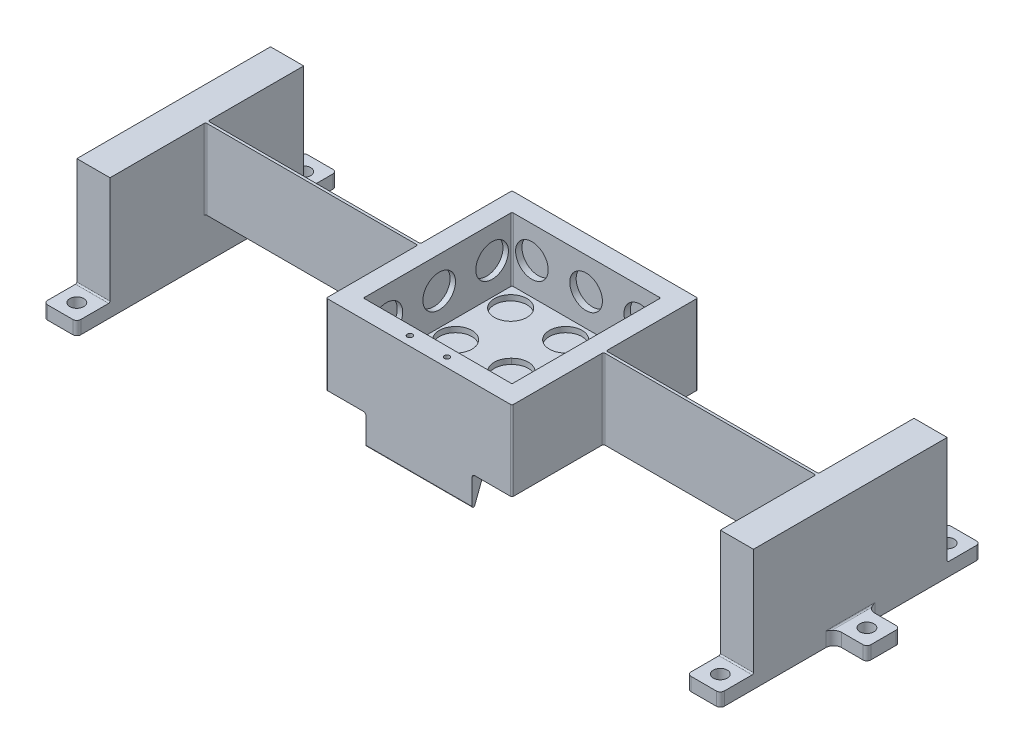
SolidWorks part; units mm, degrees
ref_plane "Front Plane" through (0, 0, 0) normal (0, 0, 1) x (1, 0, 0)
ref_plane "Top Plane" through (0, 0, 0) normal (0, 1, 0) x (1, 0, 0)
ref_plane "Right Plane" through (0, 0, 0) normal (1, 0, 0) x (0, 0, -1)
sketch "Sketch1" plane through (0, 0, 0) normal (0, 1, 0) x (1, 0, 0)
  line L1 (-35, -35) -> (35, -35)
  line L2 (-35, -35) -> (-35, 35)
  line L3 (-35, 35) -> (35, 35)
  line L4 (35, -35) -> (35, 35)
  line L5 (-35, -35) -> (35, 35) construction
  line L6 (-35, 35) -> (35, -35) construction
  point P0 (0, 0)
  dimension "D1" = 70
  dimension "D2" = 70
extrude "Boss-Extrude1" add sketch "Sketch1" along normal blind 30
shell "Shell1" thickness 7 removed face at (0, 30, 0)
sketch "Sketch2" plane through (0, 30, 0) normal (0, 1, 0) x (1, 0, 0)
  line L0 (-35, 35) -> (-35, -35) construction
  line L1 (-28, -28) -> (28, -28) construction
  line L2 (-28, -28) -> (-28, 28) construction
  line L3 (-28, 28) -> (28, 28) construction
  line L4 (28, -28) -> (28, 28) construction
  line L5 (-28, -28) -> (28, 28) construction
  line L6 (-28, 28) -> (28, -28) construction
  line L7 (35, 35) -> (-35, 35) construction
  point P0 (0, 0)
  dimension "D1" = 7
  dimension "D2" = 7
sketch "Sketch3" plane through (35, 0, 0) normal (1, 0, 0) x (0, 0, -1)
  line L0 (-35, 30) -> (35, 30) construction
  line L1 (-24, 30) -> (-23, 30) construction
  line L2 (-24, 30) -> (-24, 0) construction
  line L3 (-24, 0) -> (-23, 0) construction
  line L4 (-23, 30) -> (-23, 0) construction
  line L5 (-35, 0) -> (35, 0) construction
  line L6 (-28, 30) -> (28, 30) construction
  line L7 (-0.5, 30) -> (0.5, 30)
  line L8 (-0.5, 30) -> (-0.5, 0)
  line L9 (-0.5, 0) -> (0.5, 0)
  line L10 (0.5, 30) -> (0.5, 0)
  line L11 (28, 30) -> (-28, 30) construction
  line L12 (24, 30) -> (23, 30) construction
  line L13 (24, 30) -> (24, 0) construction
  line L14 (24, 0) -> (23, 0) construction
  line L15 (23, 30) -> (23, 0) construction
  line L16 (-23.5, 30) -> (-23.5, 0) construction
  line L17 (0, 30) -> (0, 0) construction
  line L18 (23.5, 0) -> (23.5, 30) construction
  dimension "D1" = 23
  dimension "D2" = 23
  dimension "D3" = 1
extrude "Boss-Extrude2" add sketch "Sketch3" along normal blind 80
sketch "Sketch5" plane through (115, 0, 0) normal (1, 0, 0) x (0, 0, -1)
  line L1 (-36.5, 30) -> (36.5, 30)
  line L2 (-36.5, 30) -> (-36.5, 0)
  line L3 (-36.5, 0) -> (36.5, 0)
  line L4 (36.5, 30) -> (36.5, 0)
  line L5 (28, 30) -> (-28, 30) construction
  line L6 (0.5, 0) -> (35, 0) construction
  line L8 (35, 30) -> (35, 0) construction
  line L9 (-35, 30) -> (-35, 0) construction
  dimension "D1" = 1.5
  dimension "D2" = 1.5
extrude "Boss-Extrude3" add sketch "Sketch5" along normal blind 12.5
sketch "Sketch6" plane through (0, 0, 0) normal (0, -1, 0) x (1, 0, 0)
  line L1 (115, 36.5) -> (127.5, 36.5)
  line L2 (115, 36.5) -> (115, -36.5)
  line L3 (115, -36.5) -> (127.5, -36.5)
  line L4 (127.5, 36.5) -> (127.5, -36.5)
extrude "Boss-Extrude4" add sketch "Sketch6" along normal blind 15.75
sketch "Sketch8" plane through (0, -15.75, 0) normal (0, -1, 0) x (1, 0, 0)
  line L1 (127.5, -36.5) -> (115, -36.5)
  line L2 (127.5, -36.5) -> (127.5, -49)
  line L3 (127.5, -49) -> (115, -49)
  line L4 (115, -36.5) -> (115, -49)
  line L5 (127.5, 36.5) -> (115, 36.5)
  line L6 (127.5, 36.5) -> (127.5, 49)
  line L7 (127.5, 49) -> (115, 49)
  line L8 (115, 36.5) -> (115, 49)
  line L13 (127.5, -36.5) -> (127.5, 36.5) construction
  line L14 (140, -6.25) -> (127.5, -6.25)
  line L15 (140, -6.25) -> (140, 6.25)
  line L16 (140, 6.25) -> (127.5, 6.25)
  line L17 (127.5, -6.25) -> (127.5, 6.25)
  line L18 (140, -6.25) -> (127.5, 6.25) construction
  line L19 (140, 6.25) -> (127.5, -6.25) construction
  line L20 (115, 0) -> (140, 0) construction
  line L21 (115, 0.5) -> (115, -0.5) construction
  point P13 (133.75, 0)
  point P19 (127.5, 0)
  point P20 (127.5, 0)
extrude "Boss-Extrude5" add sketch "Sketch8" against normal blind 5
hole_wizard "Ø5.0mm Dowel Hole1" positions "Sketch9" profile "Sketch10" hole size "Ø5.0" standard "ANSI Metric"
sketch "Sketch9" plane through (0, -10.75, 0) normal (0, 1, 0) x (1, 0, 0)
  line L0 (121.25, 49) -> (121.25, 42.75) construction
  line L1 (115, 49) -> (127.5, 49) construction
  line L2 (121.25, 42.75) -> (127.5, 42.75) construction
  line L3 (127.5, 49) -> (127.5, 36.5) construction
  line L5 (127.5, 0) -> (133.75, 0) construction
  line L6 (127.5, -6.25) -> (127.5, 6.25) construction
  line L7 (133.75, 0) -> (133.75, 6.25) construction
  line L8 (127.5, 6.25) -> (140, 6.25) construction
  line L10 (121.25, -36.5) -> (121.25, -42.75) construction
  line L11 (115, -36.5) -> (127.5, -36.5) construction
  line L12 (121.25, -42.75) -> (127.5, -42.75) construction
  line L13 (127.5, -36.5) -> (127.5, -49) construction
  point P0 (121.25, 42.75)
  point P2 (133.75, 0)
  point P4 (121.25, -42.75)
sketch "Sketch10" plane through (121.25, -10.75, -42.75) normal (1, 0, 0) x (0, 0, 1)
  line L0 (0, 0) -> (0, 18.1023)
  line L1 (0, 18.1023) -> (2.65, 16.51)
  line L2 (2.65, 16.51) -> (2.65, 0)
  line L5 (2.65, 0) -> (0, 0)
  line L10 (0, 18.1023) -> (-2.65, 16.51) construction
  line L11 (0, -6.35) -> (0, 107.95) construction
  dimension "Hole Dia." = 5.3
  dimension "Hole Depth" = 16.51
  dimension "Drill Angle" = 118
mirror "Mirror1" about plane through (0, 0, 0) normal (1, 0, 0) of "Boss-Extrude2", "Boss-Extrude3", "Boss-Extrude5", "Boss-Extrude4", "Ø5.0mm Dowel Hole1"
fillet "Fillet1" radius 0.5 12 edges at (-115, 15, 0.5) (-115, 15, -0.5) (-35, 15, 0.5) (-35, 15, -0.5) (-121.25, -10.75, -36.5) (-121.25, -10.75, 36.5) (35, 15, 0.5) (35, 15, -0.5) (115, 15, 0.5) (115, 15, -0.5) (121.25, -10.75, -36.5) (121.25, -10.75, 36.5)
fillet "Fillet2" radius 1.5 12 edges at (140, -13.25, 6.25) (140, -13.25, -6.25) (127.5, -13.25, -49) (115, -13.25, -49) (127.5, -13.25, 49) (115, -13.25, 49) (-115, -13.25, -49) (-127.5, -13.25, -49) (-140, -13.25, -6.25) (-140, -13.25, 6.25) (-115, -13.25, 49) (-127.5, -13.25, 49)
sketch "Sketch11" plane through (0, 6, 0) normal (0, 1, 0) x (1, 0, 0)
  line L26 (-28, -28) -> (-28, 28) construction
  line L32 (-28, -28) -> (28, -28) construction
  circle A0 centre (-21, -21) radius 6.15
  dimension "D1" = 12.3
  dimension "D2" = 0.85
  dimension "D3" = 0.85
extrude "Cut-Extrude1" cut sketch "Sketch11" against normal blind 2.05
pattern_linear "LPattern1" count 3 spacing 20.75 along (1, 0, 0) count 3 spacing 20.75 along (0, 0, -1) of "Cut-Extrude1"
sketch "Sketch14" plane through (0, 6, 0) normal (0, 1, 0) x (1, 0, 0)
  line L0 (-28, 0) -> (0, 0) construction
  line L1 (-28, 28) -> (-28, -28) construction
  line L2 (0, 0) -> (0, -28) construction
  line L3 (-28, -28) -> (28, -28) construction
  circle A0 centre (0, 0) radius 6.15
  dimension "D1" = 12.3
extrude "Cut-Extrude4" cut sketch "Sketch14" against normal blind 2.05
sketch "Sketch12" plane through (-28, 0, 0) normal (1, 0, 0) x (0, 0, -1)
  line L5 (-28, 18) -> (-19.35, 18) construction
  line L6 (-28, 30) -> (-28, 6) construction
  circle A0 centre (-19.35, 18) radius 6.15
  dimension "D1" = 12.3
  dimension "D2" = 2.5
extrude "Cut-Extrude2" cut sketch "Sketch12" against normal blind 2.05
pattern_linear "LPattern2" count 3 spacing 19.925 along (0, 0, -1) of "Cut-Extrude2"
sketch "Sketch13" plane through (0, 0, -28) normal (0, 0, -1) x (-1, 0, 0)
  line L6 (-28, 30) -> (-28, 6) construction
  line L7 (-20.35, 18) -> (-28, 18) construction
  circle A0 centre (-20.35, 18) radius 6.15
  dimension "D1" = 12.3
  dimension "D3" = 1.5
extrude "Cut-Extrude3" cut sketch "Sketch13" along normal blind 2.4
pattern_linear "LPattern3" count 3 spacing 20.425 along (-1, 0, 0) of "Cut-Extrude3"
mirror "Mirror2" about plane through (0, 0, 0) normal (1, 0, 0) of "LPattern2", "Cut-Extrude2"
fillet "Fillet3" radius 0.5 4 edges at (28, 18, -28) (-28, 18, -28) (28, 18, 28) (-28, 18, 28)
fillet "Fillet4" radius 0.5 4 edges at (-35, 15, 35) (35, 15, 35) (-35, 15, -35) (35, 15, -35)
sketch "Sketch19" plane through (0, 0, 0) normal (1, 0, 0) x (0, 0, -1)
  line L0 (-30, 0) -> (-35, -13.25)
  line L1 (-35, -13.25) -> (-35, 0)
  line L2 (-35, 0) -> (-30, 0)
  line L3 (0, 0) -> (-30, 0) construction
  line L4 (47.5, -15.75) -> (-47.5, -15.75) construction
  dimension "D1" = 5
  dimension "D2" = 30
  dimension "D3" = 2.5
extrude "Boss-Extrude8" add sketch "Sketch19" along normal mid plane 40
sketch "Sketch20" plane through (0, 0, 0) normal (1, 0, 0) x (0, 0, -1)
  line L0 (-35, 20) -> (-42.5, 20)
  line L1 (-42.5, 20) -> (-42.5, 30)
  line L2 (-36.5, 30) -> (-42.5, 30) construction
  line L5 (-42.5, 30) -> (-40, 30)
  line L6 (-40, 30) -> (-40, 22.5)
  line L7 (-40, 22.5) -> (-35, 22.5)
  line L8 (-35, 22.5) -> (-35, 20)
  line L9 (-35, 30) -> (-35, 0) construction
  line L10 (-35, 0) -> (-35, 30) construction
  dimension "D1" = 5
  dimension "D2" = 10
  dimension "D3" = 2.5
  dimension "D4" = 2.5
extrude "Place For Sensor" [suppressed] add sketch "Sketch20" along normal mid plane 10
fillet "Place For Sensor Fillet5" [suppressed] radius 0.5
fillet "Place For Sensor Fillet6" [suppressed] radius 1.5
hole_wizard "Place For Sensor Ø3.0mm Dowel Hole2" [suppressed] positions "Sketch21" profile "Sketch22" hole size "Ø3.0" standard "ANSI Metric"
sketch "Sketch21" [suppressed] plane through (0, 0, 32.5) normal (0, 0, 1) x (1, 0, 0)
  line L0 (-2.5, 27.5) -> (2.5, 27.5) construction
  line L2 (-18, 30) -> (18, 30) construction
  line L3 (-5, 28.5) -> (-5, 20.5) construction
  line L4 (5, 28.5) -> (5, 20.5) construction
  point P0 (-2.5, 27.5)
  point P2 (2.5, 27.5)
  dimension "D1" = 2.5
  dimension "D2" = 2.5
  dimension "D3" = 2.5
sketch "Sketch22" plane through (-2.5, 27.5, 32.5) normal (1, 0, 0) x (0, -1, 0)
  line L0 (0, 0) -> (0, 2.5)
  line L1 (0, 2.5) -> (1.65, 2.5)
  line L2 (1.65, 2.5) -> (1.65, 0)
  line L5 (1.65, 0) -> (0, 0)
  line L11 (0, -6.35) -> (0, 107.95) construction
  dimension "Thru Hole Dia." = 3.3
  dimension "Thru Hole Depth" = 2.5
sketch "Sketch23" plane through (0, 30, 0) normal (0, 1, 0) x (1, 0, 0)
  line L1 (-28, -28) -> (28, -28) construction
  circle A0 centre (-7, -31.5) radius 1
  circle A1 centre (7, -31.5) radius 1
  dimension "D4" = 2
  dimension "D1" = 3.5
  dimension "D2" = 14
  dimension "D3" = 7
extrude "Cut-Extrude5" cut sketch "Sketch23" against normal blind 6
fillet "Fillet5" radius 0.5 1 edges at (0, -13.25, 35)
fillet "Fillet6" radius 1 3 edges at (-20, 0, 32.5) (20, 0, 32.5) (0, 0, 30)
fillet "Fillet8" radius 3 4 edges at (127.5, -13, 6.25) (127.5, -13, -6.25) (-127.5, -13, -6.25) (-127.5, -13, 6.25)
